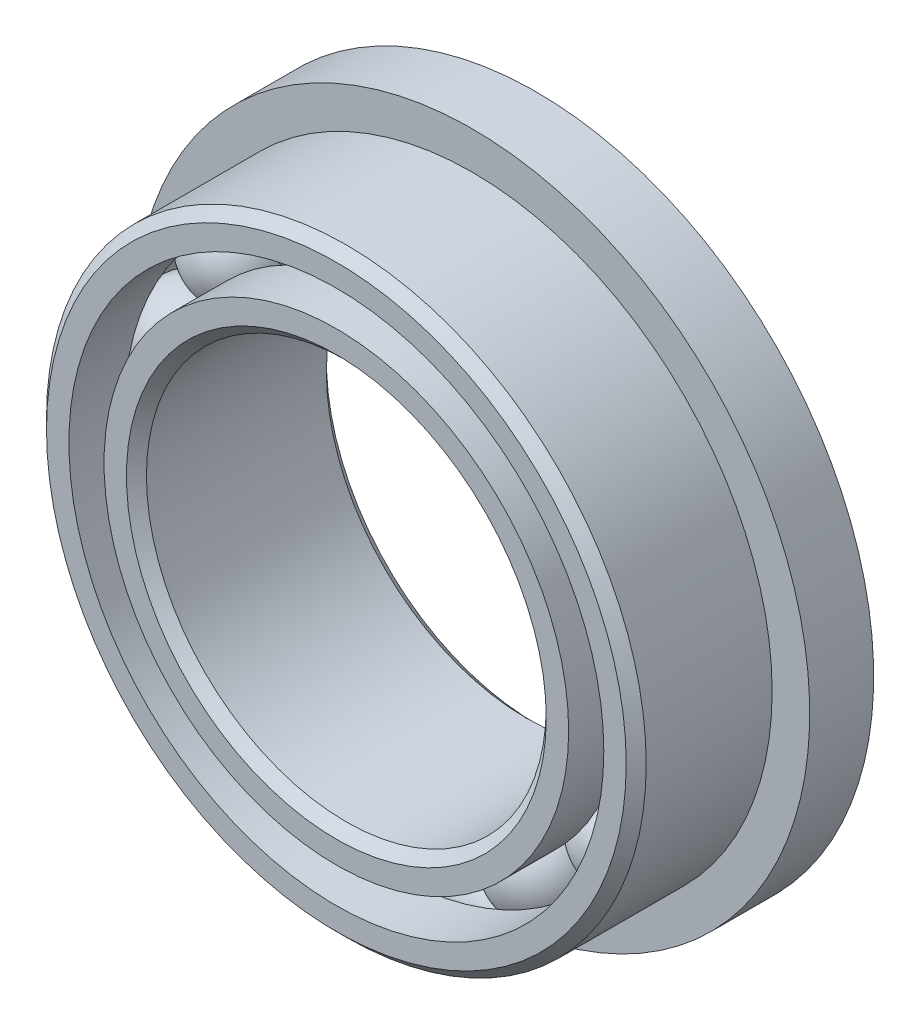
SolidWorks part; units mm, degrees
material "AISI 1020"
ref_plane "Front Plane" through (0, 0, 0) normal (0, 0, 1) x (1, 0, 0)
ref_plane "Top Plane" through (0, 0, 0) normal (0, 1, 0) x (1, 0, 0)
ref_plane "Right Plane" through (0, 0, 0) normal (1, 0, 0) x (0, 0, -1)
sketch "Sketch1" plane through (0, 0, 0) normal (1, 0, 0) x (0, 0, -1)
  line L0 (-1.5875, 0) -> (1.5875, 0) construction
  line L1 (0, 4.7625) -> (0, -4.7625) construction
  line L2 (1.4288, 4.7625) -> (-1.4288, 4.7625)
  line L3 (-1.4288, 4.7625) -> (-1.5875, 4.6037)
  line L4 (-1.5875, 4.6037) -> (-1.5875, 4.2479)
  line L5 (-1.5875, 4.2479) -> (-0.7056, 4.2479)
  line L6 (1.5875, 4.2479) -> (0.7056, 4.2479)
  line L7 (1.5875, 4.6037) -> (1.5875, 4.2479)
  line L8 (1.4288, 4.7625) -> (1.5875, 4.6037)
  line L9 (0, 4.7625) -> (0, 3.9688) construction
  line L10 (0, 3.9688) -> (0, 3.175) construction
  arc A0 (-0.7056, 4.2479) -> (0.7056, 4.2479) centre (0, 3.9688) cw
  point P14 (0, 3.175)
  dimension "D3" = 1.4111
  dimension "D1" = 45
  dimension "Width" = 3.175
  dimension "OD" = 9.525
  dimension "D2" = 0.1588
  dimension "Shaft Dia" = 6.35
  dimension "D4" = 0.2791
revolve "Revolve1" add sketch "Sketch1" angle 360 about L0
sketch "Sketch3" plane through (0, 0, 0) normal (1, 0, 0) x (0, 0, -1)
  line L0 (-1.4288, 4.7625) -> (-1.5875, 4.6037) construction
  line L1 (-0.7056, 3.6896) -> (-1.5875, 3.6896)
  line L2 (-1.5875, 4.6037) -> (-1.5875, 4.2479) construction
  line L3 (-1.5875, 3.6896) -> (-1.5875, 3.3337)
  line L5 (-1.5875, 3.3337) -> (-1.4288, 3.175)
  line L6 (-1.4288, 3.175) -> (1.4288, 3.175)
  line L7 (1.5875, 4.6037) -> (1.5875, 4.2479) construction
  line L8 (1.4288, 3.175) -> (1.5875, 3.3337)
  line L10 (1.5875, 3.3337) -> (1.5875, 3.6896)
  line L11 (1.5875, 3.6896) -> (0.7056, 3.6896)
  line L13 (1.4288, 4.7625) -> (1.5875, 4.6037) construction
  arc A1 (0.7056, 3.6896) -> (-0.7056, 3.6896) centre (0, 3.9688) cw
  arc A2 (0.7056, 4.2479) -> (-0.7056, 4.2479) centre (0, 3.9688) ccw construction
revolve "Revolve3" add sketch "Sketch3" angle 360 about L0
sketch "Sketch5" plane through (0, 0, 0) normal (1, 0, 0) x (0, 0, -1)
  line L0 (1.5875, 4.6037) -> (1.5875, 4.2479) construction
  line L1 (1.5875, 4.4258) -> (0.5715, 4.4258)
  line L2 (1.5875, 4.4258) -> (1.5875, 5.3594)
  line L3 (1.5875, 5.3594) -> (0.5715, 5.3594)
  line L4 (0.5715, 4.4258) -> (0.5715, 5.3594)
  line L5 (1.5875, 0) -> (-1.5875, 0) construction
  dimension "Th" = 1.016
  dimension "Flange OD" = 10.7188
revolve "Revolve5" add sketch "Sketch5" angle 360 about L5
sketch "Sketch4" plane through (0, 0, 0) normal (1, 0, 0) x (0, 0, -1)
  line L0 (-0.7588, 3.9688) -> (0.7588, 3.9688)
  arc A2 (-0.7588, 3.9688) -> (0.7588, 3.9688) centre (0, 3.9688) cw
  arc A3 (0.7056, 4.2479) -> (-0.7056, 4.2479) centre (0, 3.9688) ccw construction
revolve "Revolve4" add sketch "Sketch4" angle 360 about L0
ref_axis "Axis1" through (0, 0, -1.5875) along (0, 0, 1)
pattern_circular "CirPattern1" count 14 every 25.714 about axis through (0, 0, -1.5875) along (0, 0, 1) of bodies 104
equation "\"D2@Sketch1\" = \"Width@Sketch1\"*.05"
equation "\"D3@Sketch1\" = \"Width@Sketch1\"/2.25"
equation "\"D4@Sketch1\" = (((\"OD@Sketch1\"-\"Width@Sketch1\")/2)/3.25)/3.5"
equation "\"D2@CirPattern1\" = 360/\"Balls@CirPattern1\""
